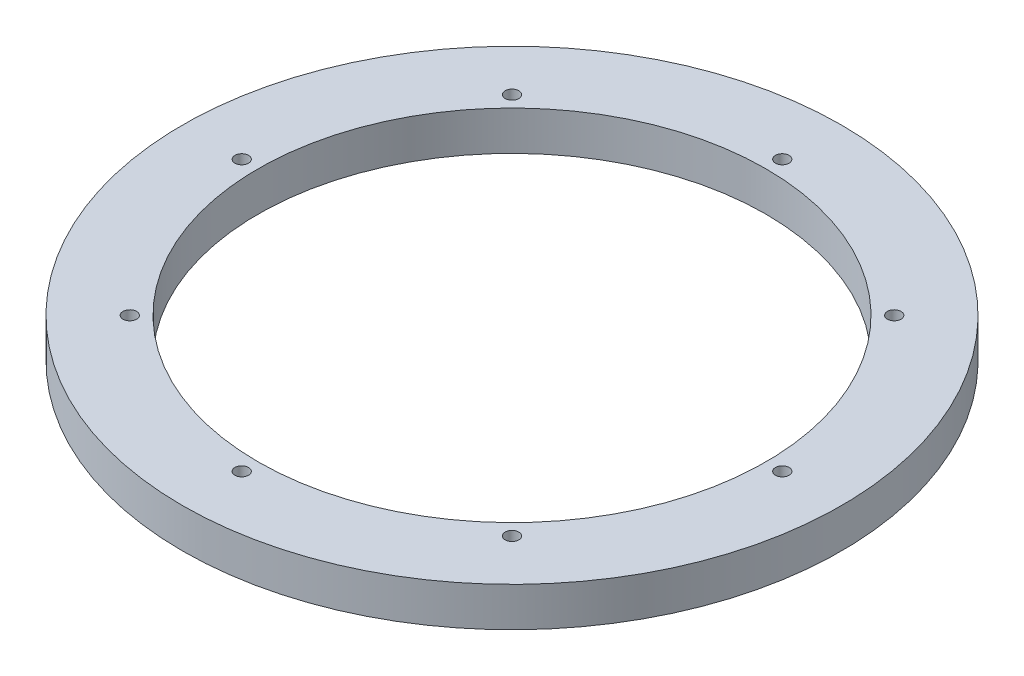
SolidWorks part; units mm, degrees
material "6061 Alloy"
ref_plane "Front Plane" through (0, 0, 0) normal (0, 0, 1) x (1, 0, 0)
ref_plane "Top Plane" through (0, 0, 0) normal (0, 1, 0) x (1, 0, 0)
ref_plane "Right Plane" through (0, 0, 0) normal (1, 0, 0) x (0, 0, -1)
sketch "Sketch1" plane through (0, 0, 0) normal (0, 1, 0) x (1, 0, 0)
  circle A0 centre (0, 0) radius 49.2125
  circle A1 centre (0, 0) radius 63.881
  circle A3 centre (0, -52.3875) radius 1.3208
  circle A4 centre (-37.0436, -37.0436) radius 1.3208
  circle A5 centre (-52.3875, 0) radius 1.3208
  circle A6 centre (-37.0436, 37.0436) radius 1.3208
  circle A7 centre (0, 52.3875) radius 1.3208
  circle A8 centre (37.0436, 37.0436) radius 1.3208
  circle A9 centre (52.3875, 0) radius 1.3208
  circle A10 centre (37.0436, -37.0436) radius 1.3208
  point P21 (0, 0)
  dimension "D1" = 98.425
  dimension "D4" = 2.6416
  dimension "D5" = 52.3875
  dimension "D2" = 14.6685
  dimension "D6" = 8
extrude "Boss-Extrude1" add sketch "Sketch1" along normal blind 7.62 contours A0 | A1 region at (-62.0742, 0, 0)
equation "\"Middle Coupler Inner Daimeter\"= 3.875in"
equation "\"Middle Coupler  Wall Thickness\" = 0.25in"
equation "\"Middle Coupler Bottom Thickness\"= 0.2in"
equation "\"Bearing Rail Offset\"= 0.45in"
equation "\"3-56 UNF Tap\"= 0.089in"
equation "\"3-56 UNF Clearance\"= 0.104in"
equation "\"D5@Sketch1\"=(\"Middle Coupler Inner Daimeter\"*2+0.5)/4in"
equation "\"Ball Bearing Distance\"= 0.03in"
equation "\"D4@Sketch1\"=\"3-56 UNF Clearance\""
equation "\"D1@Sketch1\"=\"Middle Coupler Inner Daimeter\""
equation "\"TCA Outer Diameter\" = 6in"
equation "\"Interstage Aeroframe Wall Thickness\" = 0.072in"
equation "\"Compression Spring OD\"= 0.42in"
equation "\"10-24 Tap\"= 0.157in"
equation "\"10-24 Clearance\"= 0.196in"
equation "\"Lower Stage Fuselage Wall Thickness\" = 0.25in"
equation "\"6-32 Tap\" = 0.107in"
equation "\"1/4-20 Tap\" = 0.201in"
equation "\"D2@Sketch1\"=0.5875 - 10/1000"
